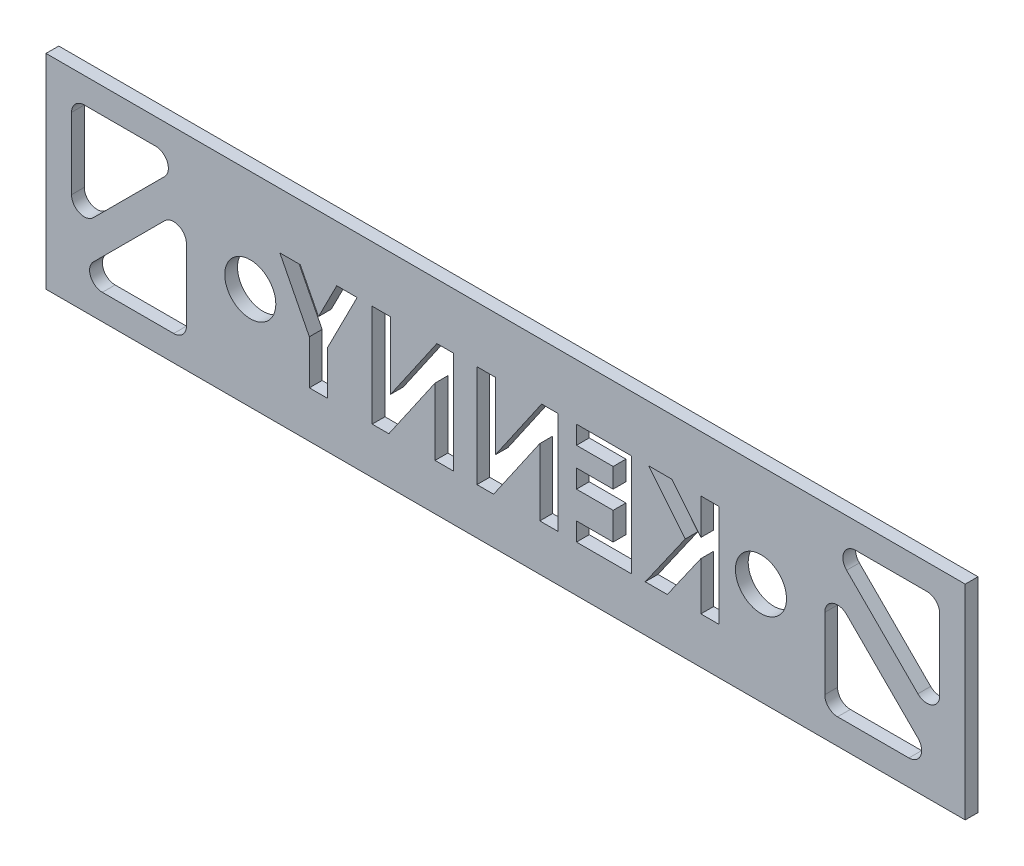
SolidWorks part; units mm, degrees
material "1060 Alloy"
ref_plane "Front Plane" through (0, 0, 0) normal (0, 0, 1) x (1, 0, 0)
ref_plane "Top Plane" through (0, 0, 0) normal (0, 1, 0) x (1, 0, 0)
ref_plane "Right Plane" through (0, 0, 0) normal (1, 0, 0) x (0, 0, -1)
sketch "Sketch1" plane through (0, 0, 0) normal (1, 0, 0) x (0, 0, -1)
  line L1 (5.0884, 8.6191) -> (-1.2616, 8.6191)
  line L2 (5.0884, 8.6191) -> (5.0884, -92.9809)
  line L3 (5.0884, -92.9809) -> (-1.2616, -92.9809)
  line L4 (-1.2616, 8.6191) -> (-1.2616, -92.9809)
  dimension "D1" = 6.35
  dimension "D2" = 101.6
extrude "Boss-Extrude1" add sketch "Sketch1" along normal blind 457.2
sketch "Sketch2" plane through (0, 0, -5.0884) normal (0, 0, -1) x (-1, 0, 0)
  line L0 (-457.2, 8.6191) -> (0, 8.6191) construction
  line L1 (0, -92.9809) -> (0, 8.6191) construction
  line L2 (-457.2, -92.9809) -> (-457.2, 8.6191) construction
  circle A0 centre (-355.6, -42.1809) radius 12.7
  circle A1 centre (-101.6, -42.1809) radius 12.7
  dimension "D1" = 25.4
  dimension "D2" = 25.4
  dimension "D3" = 50.8
  dimension "D4" = 50.8
  dimension "D5" = 101.6
  dimension "D6" = 101.6
extrude "Cut-Extrude1" cut sketch "Sketch2" against normal through all
sketch "Sketch3" plane through (0, 0, -5.0884) normal (0, 0, -1) x (-1, 0, 0)
  line L0 (-438.15, -4.0809) -> (-402.6803, -4.0809)
  line L1 (-444.5, -10.4309) -> (-444.5, -45.9006)
  line L2 (-433.6599, -50.3907) -> (-398.1901, -14.921)
  line L3 (-398.1901, -33.971) -> (-433.6599, -69.4407)
  line L4 (-429.1697, -80.2809) -> (-393.7, -80.2809)
  line L5 (-387.35, -73.9309) -> (-387.35, -38.4611)
  line L6 (-457.2, 8.6191) -> (0, 8.6191) construction
  line L7 (-457.2, -92.9809) -> (-457.2, 8.6191) construction
  line L8 (-457.2, -92.9809) -> (0, -92.9809) construction
  line L9 (-228.6, 8.6191) -> (-228.6, -92.9809) construction
  line L10 (-69.85, -73.9309) -> (-69.85, -38.4611)
  line L11 (-28.0303, -80.2809) -> (-63.5, -80.2809)
  line L12 (-59.0099, -33.971) -> (-23.5401, -69.4407)
  line L13 (-23.5401, -50.3907) -> (-59.0099, -14.921)
  line L14 (-12.7, -10.4309) -> (-12.7, -45.9006)
  line L15 (-19.05, -4.0809) -> (-54.5197, -4.0809)
  arc A0 (-398.1901, -33.971) -> (-387.35, -38.4611) centre (-393.7, -38.4611) cw
  arc A1 (-393.7, -80.2809) -> (-387.35, -73.9309) centre (-393.7, -73.9309) ccw
  arc A2 (-433.6599, -69.4407) -> (-429.1697, -80.2809) centre (-429.1697, -73.9309) ccw
  arc A3 (-444.5, -45.9006) -> (-433.6599, -50.3907) centre (-438.15, -45.9006) ccw
  arc A4 (-402.6803, -4.0809) -> (-398.1901, -14.921) centre (-402.6803, -10.4309) cw
  arc A5 (-438.15, -4.0809) -> (-444.5, -10.4309) centre (-438.15, -10.4309) ccw
  arc A6 (-19.05, -4.0809) -> (-12.7, -10.4309) centre (-19.05, -10.4309) cw
  arc A7 (-54.5197, -4.0809) -> (-59.0099, -14.921) centre (-54.5197, -10.4309) ccw
  arc A8 (-12.7, -45.9006) -> (-23.5401, -50.3907) centre (-19.05, -45.9006) cw
  arc A9 (-23.5401, -69.4407) -> (-28.0303, -80.2809) centre (-28.0303, -73.9309) cw
  arc A10 (-63.5, -80.2809) -> (-69.85, -73.9309) centre (-63.5, -73.9309) cw
  arc A11 (-59.0099, -33.971) -> (-69.85, -38.4611) centre (-63.5, -38.4611) ccw
  text T0 "KENNY" font "Century Gothic" height 50.8
  point P17 (-387.35, -80.2809)
  point P20 (-444.5, -80.2809)
  point P23 (-444.5, -61.2309)
  point P26 (-387.35, -4.0809)
  point P29 (-444.5, -4.0809)
  point P50 (-12.7, -4.0809)
  point P51 (-69.85, -4.0809)
  point P52 (-12.7, -61.2309)
  point P53 (-12.7, -80.2809)
  point P54 (-69.85, -80.2809)
  dimension "D8" = 6.35
  dimension "D1" = 12.7
  dimension "D2" = 12.7
  dimension "D3" = 12.7
  dimension "D4" = 12.7
  dimension "D5" = 57.15
  dimension "D6" = 57.15
  dimension "D7" = 57.15
extrude "Cut-Extrude2" cut sketch "Sketch3" against normal through all
